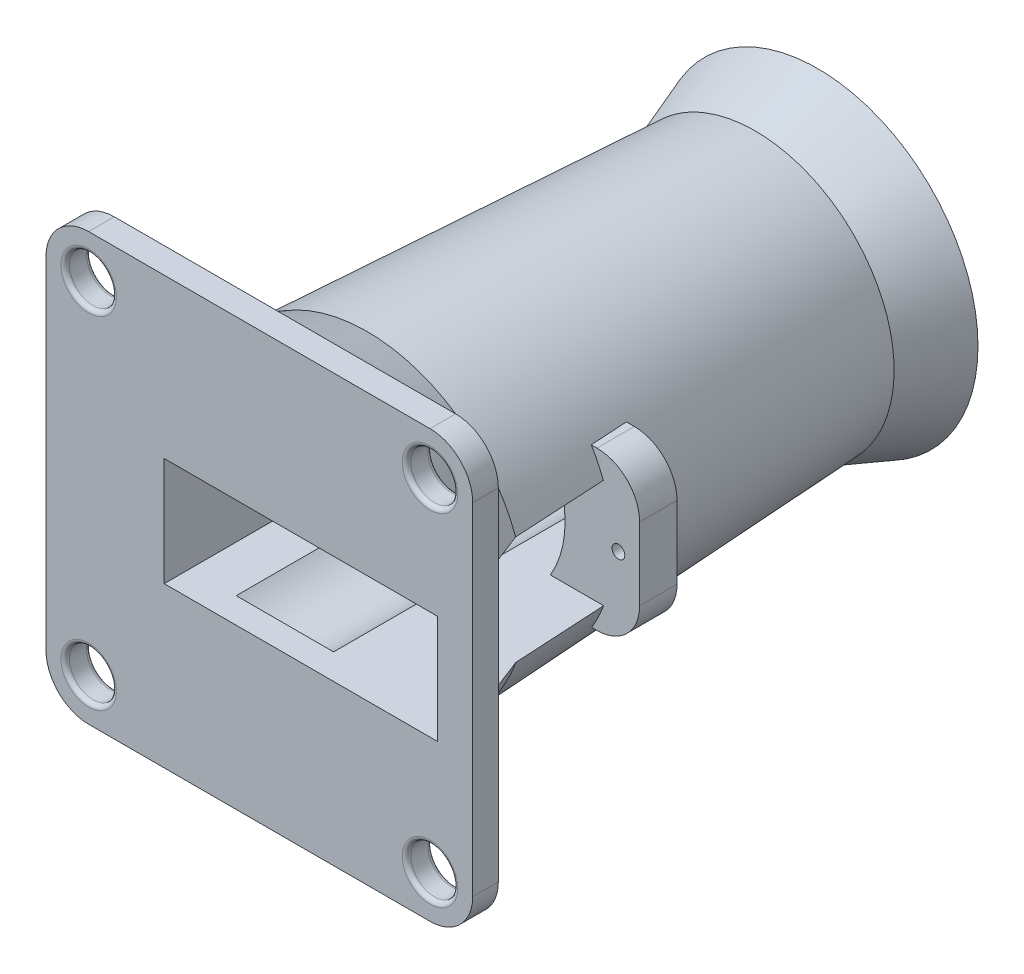
SolidWorks part; units mm, degrees
ref_plane "Front Plane" through (0, 0, 0) normal (0, 0, 1) x (1, 0, 0)
ref_plane "Top Plane" through (0, 0, 0) normal (0, 1, 0) x (1, 0, 0)
ref_plane "Right Plane" through (0, 0, 0) normal (1, 0, 0) x (0, 0, -1)
sketch "Sketch1" plane through (0, 0, 0) normal (0, 0, 1) x (1, 0, 0)
  line L0 (-4.8495, -53.6874) -> (-4.8495, 49946.3126) construction
  line L1 (20.1505, -25.049) -> (-29.8495, -25.049)
  line L2 (20.1505, -25.049) -> (20.1505, 24.951)
  line L3 (20.1505, 24.951) -> (-29.8495, 24.951)
  line L4 (-29.8495, -25.049) -> (-29.8495, 24.951)
  line L5 (20.1505, -25.049) -> (-29.8495, 24.951) construction
  line L6 (20.1505, 24.951) -> (-29.8495, -25.049) construction
  line L7 (66.767, -0.049) -> (-49933.233, -0.049) construction
  circle A0 centre (-24.8495, 19.951) radius 2.75
  circle A1 centre (-24.8495, -20.049) radius 2.75
  circle A2 centre (15.1505, 19.951) radius 2.75
  circle A3 centre (15.1505, -20.049) radius 2.75
  point P0 (-4.8495, -0.049)
  point P18 (-4.8495, -0.049)
  dimension "D3" = 5.5
  dimension "D1" = 50
  dimension "D2" = 50
  dimension "D4" = 5
extrude "Boss-Extrude1" add sketch "Sketch1" along normal blind 3
sketch "Sketch11" plane through (0, 0, 0) normal (0, 0, -1) x (-1, 0, 0)
  line L1 (-15.899, 0.6692) -> (-15.899, 6.25) construction
  line L2 (-15.899, 6.25) -> (-11.2, 6.25) construction
  line L3 (-11.2, 6.25) -> (-11.2, -6.25) construction
  line L4 (-11.2, -6.25) -> (-15.899, -6.25) construction
  line L5 (-15.899, -6.25) -> (-15.899, -0.6008) construction
  line L9 (15.899, -0.6008) -> (15.899, -6.25) construction
  line L10 (15.899, -6.25) -> (11.2, -6.25) construction
  line L11 (11.2, -6.25) -> (11.2, 6.25) construction
  line L12 (11.2, 6.25) -> (15.899, 6.25) construction
  line L13 (15.899, 6.25) -> (15.899, 0.6692) construction
  line L15 (-15.899, 0.6692) -> (-15.899, 6.25)
  line L16 (-15.899, 6.25) -> (-11.2, 6.25)
  line L17 (-11.2, 6.25) -> (-11.2, -6.25)
  line L18 (-11.2, -6.25) -> (-15.899, -6.25)
  line L19 (-15.899, -6.25) -> (-15.899, -0.6008)
  line L23 (15.899, -0.6008) -> (15.899, -6.25)
  line L24 (15.899, -6.25) -> (11.2, -6.25)
  line L25 (11.2, -6.25) -> (11.2, 6.25)
  line L26 (11.2, 6.25) -> (15.899, 6.25)
  line L27 (15.899, 6.25) -> (15.899, 0.6692)
  line L28 (-15.899, 0.6692) -> (-15.899, -0.6008)
  line L29 (15.899, 0.6692) -> (15.899, -0.6008)
extrude "Boss-Extrude5" add sketch "Sketch11" along normal blind 2
sketch "Sketch14" plane through (0, 0, 0) normal (0, 0, -1) x (-1, 0, 0)
  line L0 (-13.1283, -6.35) -> (15.999, -6.35)
  line L1 (15.999, -6.35) -> (15.999, 6.35)
  line L2 (15.999, 6.35) -> (10.4444, 6.35)
  line L3 (11.2, 6.25) -> (-11.2, 6.25) construction
  line L4 (29.8495, -25.049) -> (29.8495, 24.951)
  line L5 (29.8495, 24.951) -> (-20.1505, 24.951)
  line L6 (-20.1505, 24.951) -> (-20.1505, -25.049)
  line L7 (-20.1505, -25.049) -> (29.8495, -25.049)
  line L8 (29.8495, -25.049) -> (29.8495, 24.951)
  line L9 (29.8495, 24.951) -> (-20.1505, 24.951)
  line L10 (-20.1505, 24.951) -> (-20.1505, -25.049)
  line L11 (-20.1505, -25.049) -> (29.8495, -25.049)
  line L12 (15.899, -6.25) -> (15.899, 6.25) construction
  line L13 (11.2, -6.25) -> (15.899, -6.25) construction
  line L14 (-0.7455, 6.35) -> (-13.0937, 6.35)
  line L16 (2.3575, -0.249) -> (-2.6479, -0.249)
  line L17 (-2.6479, 0.151) -> (2.3575, 0.151)
  line L18 (2.3575, -0.249) -> (-2.6479, -0.249) construction
  line L19 (-2.6479, 0.151) -> (2.3575, 0.151) construction
  arc A0 (10.4444, 6.35) -> (-0.7455, 6.35) centre (4.8495, -0.049) ccw
  circle A1 centre (4.8495, -0.049) radius 19.05
  arc A2 (-13.1283, -6.35) -> (-13.0937, 6.35) centre (4.8495, -0.049) ccw
  arc A3 (-0.8556, -6.35) -> (10.5545, -6.35) centre (4.8495, -0.049) ccw
  arc A4 (2.3575, -0.249) -> (2.3575, 0.151) centre (4.8495, -0.049) ccw
  arc A5 (-2.6479, -0.249) -> (-2.6479, 0.151) centre (4.8495, -0.049) ccw
  arc A6 (2.3575, -0.249) -> (2.3575, 0.151) centre (4.8495, -0.049) ccw construction
  arc A7 (-2.6479, -0.249) -> (-2.6479, 0.151) centre (4.8495, -0.049) ccw construction
  dimension "D7" = 1
  dimension "D3" = 0.1
  dimension "D4" = 0.1
  dimension "D5" = 0.1
  dimension "D1" = 0
  dimension "D2" = 0
  dimension "D6" = 0
extrude "Boss-Extrude6" add sketch "Sketch14" along normal offset from surface (62.4298 mm away) 0.1 contours L0 A2 L2 L1
draft "Draft1" type of draft neutral plane draft angle 3 faces to draft 1 face at (-5.3942, -0.0505, -31.2149) neutral plane through (0, 0, 0) neutral plane normal (0, 0, -1) parameters "D1"=3
sketch "Sketch15" plane through (0, 0, -2) normal (0, 0, -1) x (-1, 0, 0)
  line L4 (-15.899, 6.25) -> (-15.899, -6.25)
  line L5 (-15.899, -6.25) -> (-11.2, -6.25)
  line L6 (-11.2, -6.25) -> (-11.2, 6.25)
  line L7 (-11.2, 6.25) -> (-15.899, 6.25)
  line L8 (-15.899, 6.25) -> (-15.899, -6.25)
  line L9 (-15.899, -6.25) -> (-11.2, -6.25)
  line L11 (-11.2, 6.25) -> (-15.899, 6.25)
  line L12 (15.899, -6.25) -> (15.899, 6.25)
  line L13 (15.899, 6.25) -> (11.2, 6.25)
  line L14 (11.2, 6.25) -> (11.2, -6.25)
  line L15 (11.2, -6.25) -> (15.899, -6.25)
  line L16 (15.899, -6.25) -> (15.899, 6.25)
  line L17 (15.899, 6.25) -> (11.2, 6.25)
  line L18 (11.2, 6.25) -> (11.2, -6.25)
  line L19 (11.2, -6.25) -> (15.899, -6.25)
  line L20 (-11.2, -6.25) -> (-11.2, 6.25)
  dimension "D1" = 0
  dimension "D2" = 0
extrude "Cut-Extrude5" cut sketch "Sketch15" against normal up to surface (2 mm away) up to face at (13.5495, 0, 0)
sketch "Sketch16" plane through (0, 0, 3) normal (0, 0, 1) x (1, 0, 0)
  line L0 (-0.1, 0) -> (-0.1, -6.25)
  line L1 (11.2, 6.25) -> (11.2, -6.25) construction
  line L2 (11.2, -6.25) -> (-11.2, -6.25) construction
  line L4 (11.2, 6.25) -> (-11.2, 6.25) construction
  line L5 (0, 0) -> (0, -6.25)
  line L6 (15.899, 0.6692) -> (15.899, -0.6008) construction
  line L7 (15.0585, 0.6692) -> (15.899, 0.6692)
  line L8 (15.899, 0.6692) -> (15.899, 6.25)
  line L9 (15.899, 6.25) -> (11.2, 6.25)
  line L10 (11.2, 6.25) -> (11.2, -6.25)
  line L11 (11.2, -6.25) -> (15.899, -6.25)
  line L12 (15.899, -6.25) -> (15.899, -0.6008)
  line L13 (15.899, -0.6008) -> (15.0904, -0.6008)
  line L15 (15.899, 0.6692) -> (15.899, 6.25) construction
  line L16 (15.899, 6.25) -> (11.2, 6.25) construction
  line L18 (11.2, -6.25) -> (15.899, -6.25) construction
  line L19 (15.899, -6.25) -> (15.899, -0.6008) construction
  line L21 (-15.899, -6.25) -> (-15.899, -0.6008) construction
  line L22 (-11.2, -6.25) -> (-15.899, -6.25) construction
  line L23 (-15.899, -0.6008) -> (-15.899, 0.6692) construction
  line L24 (-15.899, 6.25) -> (-11.2, 6.25) construction
  line L25 (-15.899, 0.6692) -> (-15.899, 6.25) construction
  line L26 (11.2, -6.35) -> (-11.2, -6.35)
  line L27 (-11.2, -6.35) -> (-15.999, -6.35)
  line L28 (-15.999, -6.35) -> (-15.999, -0.6008)
  line L29 (-15.999, -0.6008) -> (-15.999, 0.6692)
  line L30 (-15.999, 0.6692) -> (-15.999, 6.35)
  line L31 (-15.999, 6.35) -> (-11.2, 6.35)
  line L32 (11.2, 6.35) -> (-11.2, 6.35)
  line L33 (15.999, 6.35) -> (11.2, 6.35)
  line L34 (15.999, 0.6692) -> (15.999, 6.35)
  line L35 (15.999, 0.6692) -> (15.999, -0.6008)
  line L36 (15.999, -6.35) -> (15.999, -0.6008)
  line L37 (11.2, -6.35) -> (15.999, -6.35)
  arc A1 (15.0585, 0.6692) -> (15.0904, -0.6008) centre (13.716, 0) ccw
  point P15 (0, -6.25)
  point P25 (0, 6.25)
  dimension "D1" = 0
  dimension "D2" = 0.1
extrude "Cut-Extrude6" cut sketch "Sketch16" against normal up to surface (3 mm away)
sketch "Sketch18" plane through (0, 0, -20.5062) normal (0, 0, -1) x (-1, 0, 0)
  line L1 (-8.2, 9.25) -> (-16.2, 9.25)
  line L2 (-8.2, -9.25) -> (-16.2, -9.25)
  line L3 (-16.2, 9.25) -> (-16.2, -9.25)
  line L4 (-11.2, 6.25) -> (-15.899, 6.25) construction
  line L5 (-11.2, -6.25) -> (-15.899, -6.25) construction
  line L6 (-8.2, 9.25) -> (-8.2, 7.25)
  line L7 (-11.2, 6.25) -> (-11.2, -6.25) construction
  line L9 (-8.2, 7.25) -> (-11.3, 7.25)
  line L10 (-8.2, -7.25) -> (-11.3, -7.25)
  line L11 (-11.3, 7.25) -> (-11.3, -7.25)
  line L12 (-8.2, -7.25) -> (-8.2, -9.25)
  dimension "D1" = 3
  dimension "D2" = 3
  dimension "D3" = 8
  dimension "D4" = 5
  dimension "D5" = 3.1
  dimension "D6" = 2
  dimension "D7" = 2
extrude "Boss-Extrude7" add sketch "Sketch18" along normal up to surface (4.3858 mm away)
sketch "Sketch19" plane through (0, 0, -24.892) normal (0, 0, -1) x (-1, 0, 0)
  arc A0 (-15.0904, -0.6008) -> (-15.0585, 0.6692) centre (-13.716, 0) ccw construction
  arc A1 (-15.0904, -0.6008) -> (-15.0585, 0.6692) centre (-13.716, 0) ccw construction
  arc A2 (-15.0585, 0.6692) -> (-15.0904, -0.6008) centre (-13.716, 0) ccw construction
  circle A3 centre (-13.716, 0) radius 0.75
  dimension "D1" = 1.5
extrude "Cut-Extrude7" cut sketch "Sketch19" against normal up to surface (4.3858 mm away) up to face at (12.5237, 0.0001, -20.5062)
sketch "Sketch26" plane through (0, 0, -20.5062) normal (0, 0, 1) x (1, 0, 0)
  line L0 (11.7397, -6.35) -> (5.7397, -6.35)
  line L6 (0.7455, 6.35) -> (9.5729, 6.35) construction
  line L7 (5.6807, 6.35) -> (11.7021, 6.35)
  arc A1 (11.7021, 6.35) -> (10.2645, 9.25) centre (-4.8495, -0.049) ccw construction
  arc A2 (10.3243, -9.25) -> (11.7397, -6.35) centre (-4.8495, -0.049) ccw construction
  arc A3 (11.7021, 6.35) -> (10.2645, 9.25) centre (-4.8495, -0.049) ccw construction
  arc A4 (10.3243, -9.25) -> (11.7397, -6.35) centre (-4.8495, -0.049) ccw construction
  arc A5 (11.7021, 6.35) -> (11.7397, -6.35) centre (-4.8495, -0.049) cw
  arc A6 (5.7397, -6.35) -> (5.6807, 6.35) centre (-4.8495, -0.049) ccw
  point P15 (0, 0)
  dimension "D1" = 6
extrude "Boss-Extrude12" add sketch "Sketch26" against normal up to surface (41.9236 mm away) up to face at (-7.8036, -0.0251, -62.4298)
draft "Draft2" type of draft neutral plane draft angle 3 faces to draft 1 face at (12.3084, 0.0017, -43.6609) neutral plane through (0, 0, -24.892) neutral plane normal (0, 0, -1) parameters "D1"=3
fillet "Fillet2" radius 5 4 edges at (-29.8495, 24.951, 1.5) (-29.8495, -25.049, 1.5) (20.1505, -25.049, 1.5) (20.1505, 24.951, 1.5)
fillet "Fillet3" radius 0.5 8 edges at (-22.0995, 19.951, 0) (-22.0995, 19.951, 3) (-27.5995, -20.049, 0) (-27.5995, -20.049, 3) (12.4005, 19.951, 0) (12.4005, 19.951, 3) (17.9005, -20.049, 0) (17.9005, -20.049, 3)
fillet "Fillet4" radius 5 2 edges at (16.2, 9.25, -22.6991) (16.2, -9.25, -22.6991)
chamfer "Chamfer1" distance 3 angle 70 1 edges at (-23.8994, -0.1009, 0)
sketch "Sketch27" plane through (0, 0, 0) normal (0, 1, 0) x (1, 0, 0)
  line L0 (10.9287, 62.4298) -> (13.9287, 62.4298)
  line L1 (13.9287, 62.4298) -> (11.3063, 55.2248)
  line L2 (12.896, 24.892) -> (10.9287, 62.4298) construction
  line L4 (-4.8495, 62.4298) -> (-4.8495, -49937.5702) construction
  line L5 (0.7455, 62.4298) -> (-10.4444, 62.4298) construction
  line L6 (10.9287, 62.4298) -> (9.9287, 62.4298)
  line L7 (10.9287, 62.4298) -> (-20.6276, 62.4298) construction
  line L8 (9.9287, 62.4298) -> (9.9287, 51.4399)
  line L9 (9.9287, 51.4399) -> (11.3063, 55.2248)
  point P10 (-4.8495, 62.4298)
  dimension "D1" = 3
  dimension "D2" = 70
  dimension "D3" = 1
revolve "Revolve4" add sketch "Sketch27" angle 360 about L4
